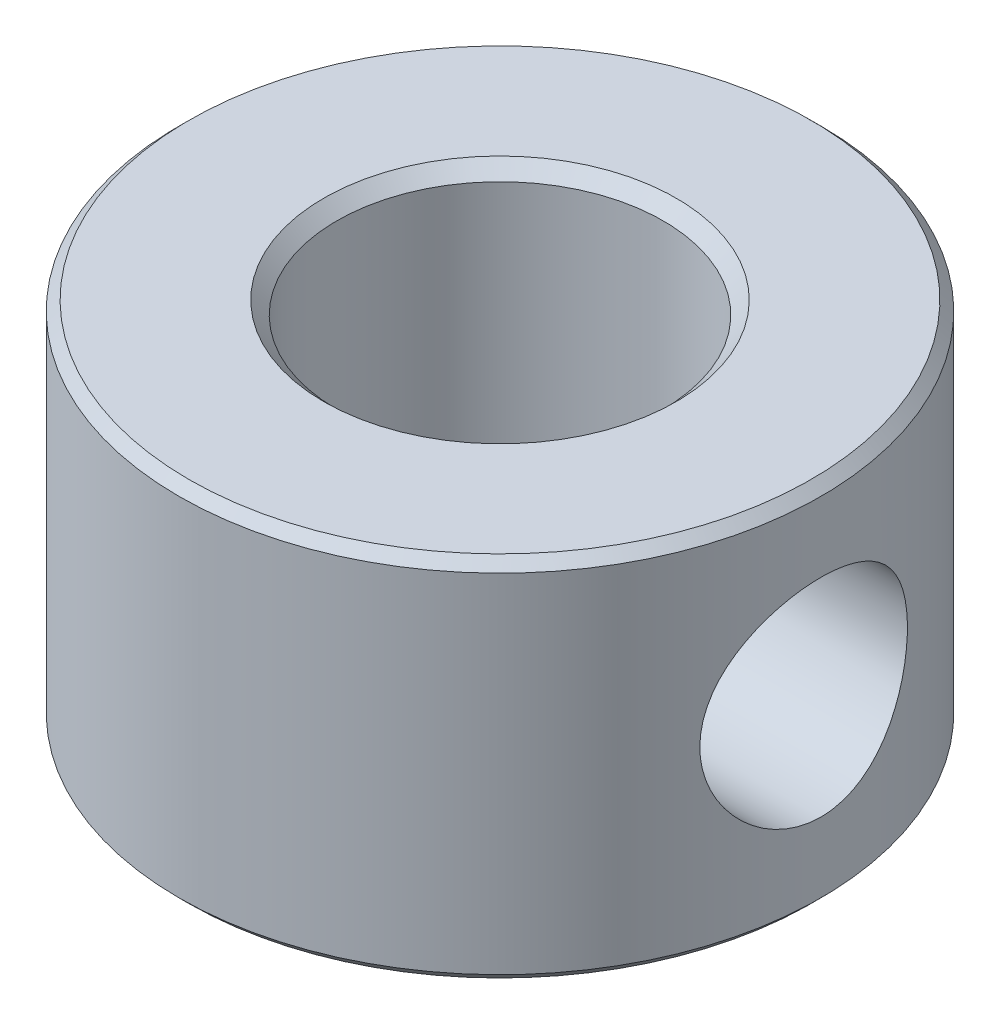
SolidWorks part; units mm, degrees
ref_plane "Front Plane" through (0, 0, 0) normal (0, 0, 1) x (1, 0, 0)
ref_plane "Top Plane" through (0, 0, 0) normal (0, 1, 0) x (1, 0, 0)
ref_plane "Right Plane" through (0, 0, 0) normal (1, 0, 0) x (0, 0, -1)
sketch "Sketch1" plane through (0, 0, 0) normal (0, 1, 0) x (1, 0, 0)
  circle A0 centre (0, 0) radius 3.175
  circle A1 centre (0, 0) radius 6.242
  dimension "D1" = 12.4841
  dimension "D2" = 6.35
extrude "Boss-Extrude1" add sketch "Sketch1" along normal blind 7.145
chamfer "Chamfer1" distance 0.1905 angle 45 2 edges at (0, 0, 6.2421) (0, 7.145, 6.2421)
chamfer "Chamfer2" distance 0.254 angle 45 2 edges at (0, 7.145, 3.175) (0, 0, 3.175)
hole_wizard "#10-32 Tapped Hole1" positions "Sketch4" profile "Sketch3" tap size "#10-32" standard "ANSI Inch" end condition through all
sketch "Sketch4" plane through (0, 0, 0) normal (1, 0, 0) x (0, 0, -1)
  line L0 (0, 3.5725) -> (0, 0) construction
  line L2 (0, 3.5725) -> (6.2421, 3.5725) construction
  line L3 (6.2421, 0.1905) -> (6.2421, 6.9545) construction
  point P1 (0, 3.5725)
sketch "Sketch3" plane through (0, 3.5725, 0) normal (0, 1, 0) x (0, 0, 1)
  line L0 (0, 0) -> (0, 6.2421)
  line L1 (0, 6.2421) -> (2.0193, 6.2421)
  line L2 (2.0193, 6.2421) -> (2.0193, 0)
  line L5 (2.0193, 0) -> (0, 0)
  line L11 (0, -6.35) -> (0, 107.95) construction
  dimension "Thru Tap Drill Dia." = 4.0386
  dimension "Thru Tap Drill Depth" = 6.2421
cosmetic thread "Hole Thread1" parameters "D2"=4.826
